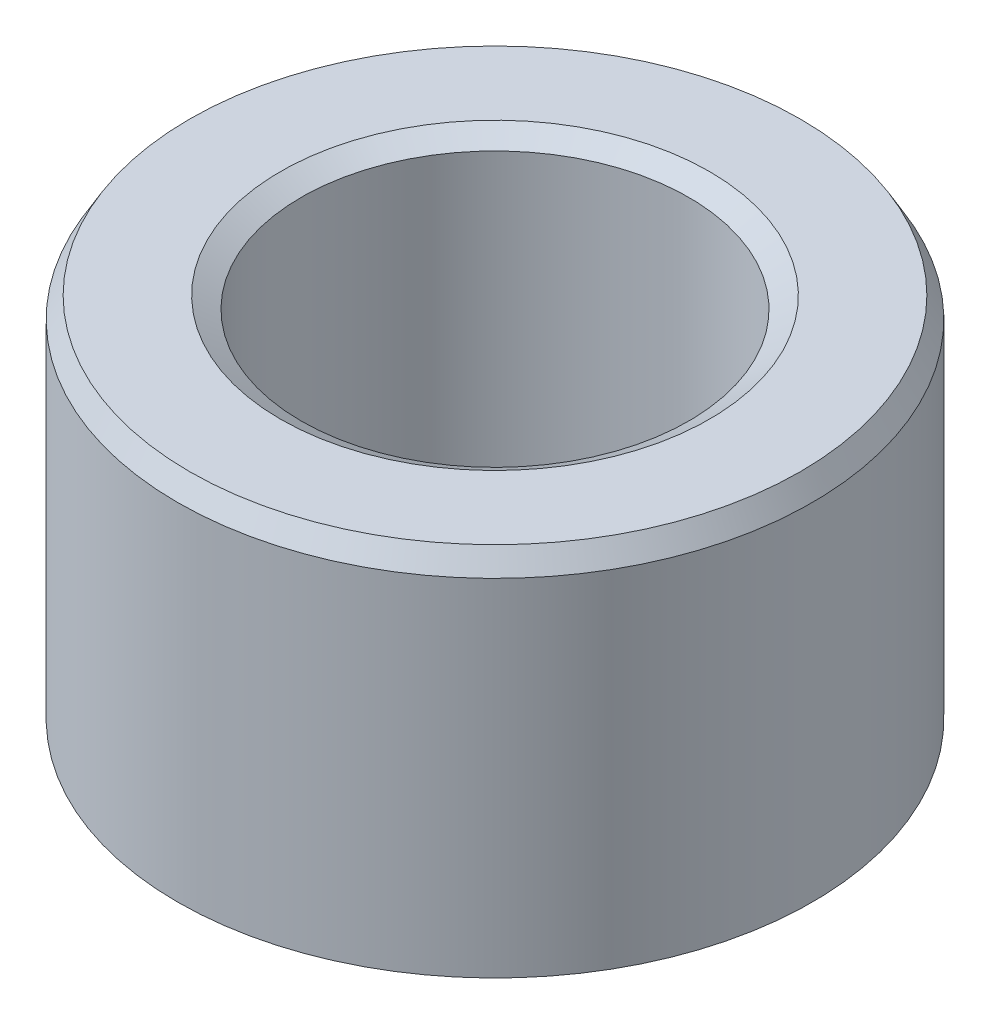
SolidWorks part; units mm, degrees
ref_plane "Front Plane" through (0, 0, 0) normal (0, 0, 1) x (1, 0, 0)
ref_plane "Top Plane" through (0, 0, 0) normal (0, 1, 0) x (1, 0, 0)
ref_plane "Right Plane" through (0, 0, 0) normal (1, 0, 0) x (0, 0, -1)
sketch "Sketch1" plane through (0, 0, 0) normal (0, 1, 0) x (1, 0, 0)
  circle A0 centre (0, 0) radius 40
  dimension "SLEEVE_OD" = 80
extrude "Boss-Extrude1" add sketch "Sketch1" along normal blind 47.7406
sketch "Sketch2" plane through (0, 0, 0) normal (0, 1, 0) x (1, 0, 0)
  circle A0 centre (0, 0) radius 24.4248
  dimension "BORE_D" = 48.8497
extrude "Cut-Extrude1" cut sketch "Sketch2" along normal through all
chamfer "Chamfer1" distance 2.613 angle 30 4 edges at (0, 47.7406, 24.4248) (0, 0, 24.4248) (0, 0, 40) (0, 47.7406, 40) first distance on face at (0, 47.7406, 24.4248) first distance on face at (0, 0, 24.4248) first distance on face at (0, 47.7406, 40)
